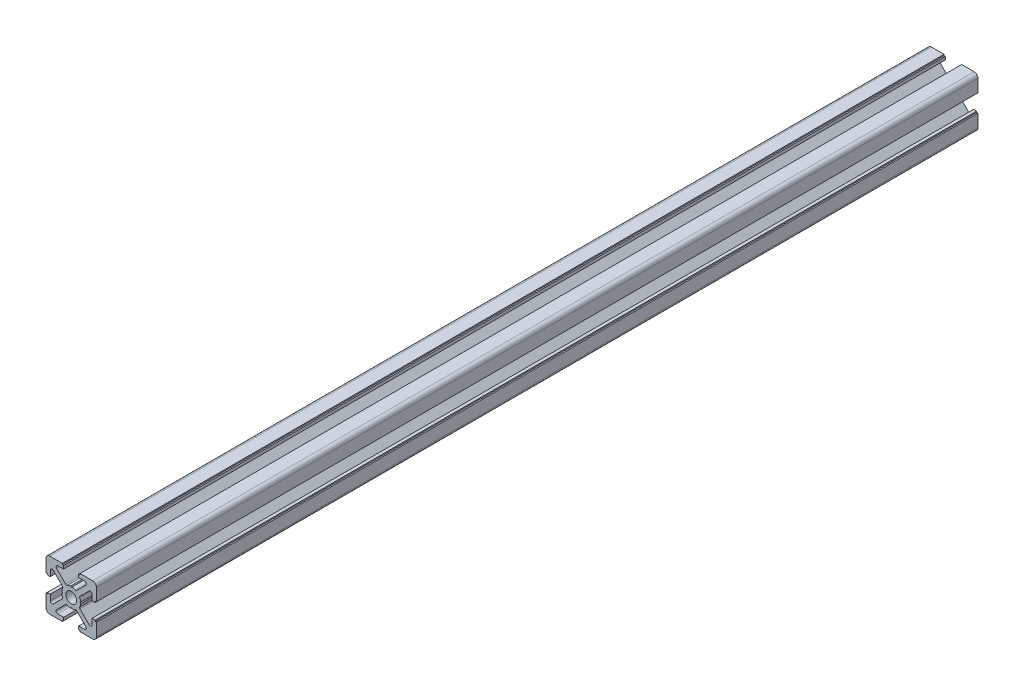
SolidWorks part; units mm, degrees
ref_plane "Alzado" through (0, 0, 0) normal (0, 0, 1) x (1, 0, 0)
ref_plane "Planta" through (0, 0, 0) normal (0, 1, 0) x (1, 0, 0)
ref_plane "Vista lateral" through (0, 0, 0) normal (1, 0, 0) x (0, 0, -1)
sketch "Model" plane through (0, 0, 0) normal (0, 0, 1) x (1, 0, 0)
  line L0 (-3.5, -9.5) -> (-3.5, -10)
  line L1 (-3.5, -10) -> (-8.5, -10)
  line L2 (-10, -8.5) -> (-10, -3.5)
  line L3 (-10, -3.5) -> (-9.5, -3.5)
  line L4 (-9.5, -3.5) -> (-9.5, -3)
  line L5 (-9.5, -3) -> (-8.3, -3)
  line L6 (-8.3, -3) -> (-8.3, -5.2994)
  line L7 (-7.105, -5.7944) -> (-3.4861, -2.1755)
  line L8 (-3.738, -0.3) -> (-3.45, 0)
  line L9 (-3.45, 0) -> (-3.738, 0.3)
  line L10 (-3.4861, 2.1755) -> (-7.105, 5.7944)
  line L11 (-8.3, 5.2994) -> (-8.3, 3)
  line L12 (-8.3, 3) -> (-9.5, 3)
  line L13 (-9.5, 3) -> (-9.5, 3.5)
  line L14 (-9.5, 3.5) -> (-10, 3.5)
  line L15 (-10, 3.5) -> (-10, 8.5)
  line L16 (-8.5, 10) -> (-3.5, 10)
  line L17 (-3.5, 10) -> (-3.5, 9.5)
  line L18 (-3.5, 9.5) -> (-3, 9.5)
  line L19 (-3, 9.5) -> (-3, 8.3)
  line L20 (-3, 8.3) -> (-5.2994, 8.3)
  line L21 (-5.7944, 7.105) -> (-2.1755, 3.4861)
  line L22 (-0.3, 3.738) -> (0, 3.45)
  line L23 (0, 3.45) -> (0.3, 3.738)
  line L24 (2.1755, 3.4861) -> (5.7944, 7.105)
  line L25 (5.2994, 8.3) -> (3, 8.3)
  line L26 (3, 8.3) -> (3, 9.5)
  line L27 (3, 9.5) -> (3.5, 9.5)
  line L28 (3.5, 9.5) -> (3.5, 10)
  line L29 (3.5, 10) -> (8.5, 10)
  line L30 (10, 8.5) -> (10, 3.5)
  line L31 (10, 3.5) -> (9.5, 3.5)
  line L32 (9.5, 3.5) -> (9.5, 3)
  line L33 (9.5, 3) -> (8.3, 3)
  line L34 (8.3, 3) -> (8.3, 5.2994)
  line L35 (7.105, 5.7944) -> (3.4861, 2.1755)
  line L36 (3.738, 0.3) -> (3.45, 0)
  line L37 (3.45, 0) -> (3.738, -0.3)
  line L38 (3.4861, -2.1755) -> (7.105, -5.7944)
  line L39 (8.3, -5.2994) -> (8.3, -3)
  line L40 (8.3, -3) -> (9.5, -3)
  line L41 (9.5, -3) -> (9.5, -3.5)
  line L42 (9.5, -3.5) -> (10, -3.5)
  line L43 (10, -3.5) -> (10, -8.5)
  line L44 (8.5, -10) -> (3.5, -10)
  line L45 (3.5, -10) -> (3.5, -9.5)
  line L46 (3.5, -9.5) -> (3, -9.5)
  line L47 (3, -9.5) -> (3, -8.3)
  line L48 (3, -8.3) -> (5.2994, -8.3)
  line L49 (5.7944, -7.105) -> (2.1755, -3.4861)
  line L50 (0.3, -3.738) -> (0, -3.45)
  line L51 (0, -3.45) -> (-0.3, -3.738)
  line L52 (-2.1755, -3.4861) -> (-5.7944, -7.105)
  line L53 (-5.2994, -8.3) -> (-3, -8.3)
  line L54 (-3, -8.3) -> (-3, -9.5)
  line L55 (-3, -9.5) -> (-3.5, -9.5)
  arc A0 (-5.7944, -7.105) -> (-5.9994, -7.6) centre (-5.2994, -7.6) ccw
  arc A1 (5.9994, -7.6) -> (5.7944, -7.105) centre (5.2994, -7.6) ccw
  arc A2 (3.388, -1.6076) -> (3.3397, -1.8219) centre (3.8397, -1.8219) ccw
  arc A3 (3.4861, 2.1755) -> (3.3397, 1.8219) centre (3.8397, 1.8219) ccw
  arc A4 (5.9994, 7.6) -> (5.2994, 8.3) centre (5.2994, 7.6) ccw
  arc A5 (-5.2994, 8.3) -> (-5.9994, 7.6) centre (-5.2994, 7.6) ccw
  arc A6 (-3.3397, 1.8219) -> (-3.4861, 2.1755) centre (-3.8397, 1.8219) ccw
  arc A7 (-3.3397, -1.8219) -> (-3.388, -1.6076) centre (-3.8397, -1.8219) ccw
  arc A8 (-2.15, 0) -> (2.15, 0) centre (0, 0) ccw
  arc A9 (2.15, 0) -> (-2.15, 0) centre (0, 0) ccw
  arc A10 (-10, -8.5) -> (-8.5, -10) centre (-8.5, -8.5) ccw
  arc A11 (-8.3, -5.2994) -> (-7.105, -5.7944) centre (-7.6, -5.2994) ccw
  arc A12 (-3.4861, -2.1755) -> (-3.3397, -1.8219) centre (-3.8397, -1.8219) ccw
  arc A13 (-3.738, -0.3) -> (-3.388, -1.6076) centre (0, 0) ccw
  arc A14 (-3.388, 1.6076) -> (-3.738, 0.3) centre (0, 0) ccw
  arc A15 (-3.388, 1.6076) -> (-3.3397, 1.8219) centre (-3.8397, 1.8219) ccw
  arc A16 (-7.105, 5.7944) -> (-8.3, 5.2994) centre (-7.6, 5.2994) ccw
  arc A17 (-8.5, 10) -> (-10, 8.5) centre (-8.5, 8.5) ccw
  arc A18 (-5.9994, 7.6) -> (-5.7944, 7.105) centre (-5.2994, 7.6) ccw
  arc A19 (-2.1755, 3.4861) -> (-1.6076, 3.388) centre (-1.8219, 3.8397) ccw
  arc A20 (-0.3, 3.738) -> (-1.6076, 3.388) centre (0, 0) ccw
  arc A21 (1.6076, 3.388) -> (0.3, 3.738) centre (0, 0) ccw
  arc A22 (1.6076, 3.388) -> (2.1755, 3.4861) centre (1.8219, 3.8397) ccw
  arc A23 (5.7944, 7.105) -> (5.9994, 7.6) centre (5.2994, 7.6) ccw
  arc A24 (10, 8.5) -> (8.5, 10) centre (8.5, 8.5) ccw
  arc A25 (8.3, 5.2994) -> (7.105, 5.7944) centre (7.6, 5.2994) ccw
  arc A26 (3.3397, 1.8219) -> (3.388, 1.6076) centre (3.8397, 1.8219) ccw
  arc A27 (3.738, 0.3) -> (3.388, 1.6076) centre (0, 0) ccw
  arc A28 (3.388, -1.6076) -> (3.738, -0.3) centre (0, 0) ccw
  arc A29 (3.3397, -1.8219) -> (3.4861, -2.1755) centre (3.8397, -1.8219) ccw
  arc A30 (7.105, -5.7944) -> (8.3, -5.2994) centre (7.6, -5.2994) ccw
  arc A31 (8.5, -10) -> (10, -8.5) centre (8.5, -8.5) ccw
  arc A32 (5.2994, -8.3) -> (5.9994, -7.6) centre (5.2994, -7.6) ccw
  arc A33 (2.1755, -3.4861) -> (1.6076, -3.388) centre (1.8219, -3.8397) ccw
  arc A34 (0.3, -3.738) -> (1.6076, -3.388) centre (0, 0) ccw
  arc A35 (-1.6076, -3.388) -> (-0.3, -3.738) centre (0, 0) ccw
  arc A36 (-1.6076, -3.388) -> (-2.1755, -3.4861) centre (-1.8219, -3.8397) ccw
  arc A37 (-5.9994, -7.6) -> (-5.2994, -8.3) centre (-5.2994, -7.6) ccw
extrude "Saliente-Extruir1" add sketch "Model" along normal blind 350
